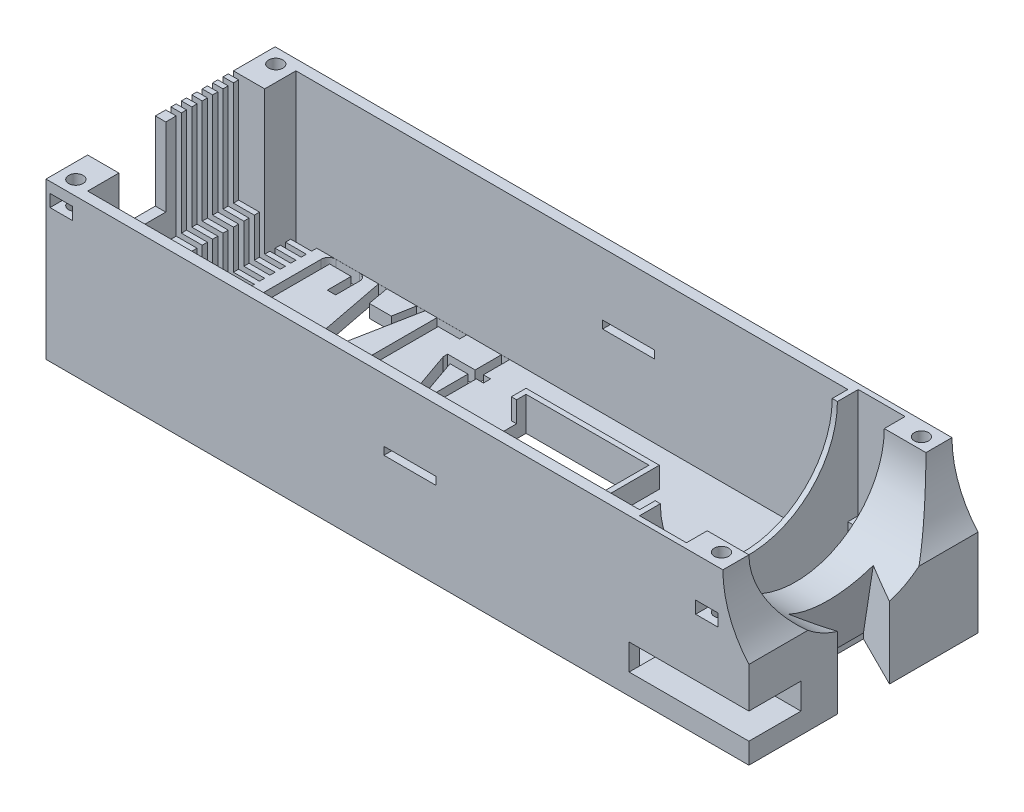
SolidWorks part; units mm, degrees
ref_plane "Front Plane" through (0, 0, 0) normal (0, 0, 1) x (1, 0, 0)
ref_plane "Top Plane" through (0, 0, 0) normal (0, 1, 0) x (1, 0, 0)
ref_plane "Right Plane" through (0, 0, 0) normal (1, 0, 0) x (0, 0, -1)
sketch "Sketch2" plane through (0, 0, 0) normal (0, 1, 0) x (1, 0, 0)
  line L4 (451.485, -2.54) -> (374.015, -2.54)
  line L5 (451.485, -2.54) -> (451.485, 74.93)
  line L6 (451.485, 74.93) -> (374.015, 74.93)
  line L7 (374.015, -2.54) -> (374.015, 74.93)
  line L8 (469.9, -19.685) -> (-50.8, -19.685)
  line L9 (469.9, -19.685) -> (469.9, 92.075)
  line L10 (469.9, 92.075) -> (-50.8, 92.075)
  line L11 (-50.8, -19.685) -> (-50.8, 92.075)
  line L12 (449.58, -0.635) -> (317.5, -0.635)
  line L13 (449.58, -0.635) -> (449.58, 89.789)
  line L14 (449.58, 89.789) -> (317.5, 89.789)
  line L15 (317.5, -0.635) -> (317.5, 89.789)
  line L16 (445.77, 3.175) -> (326.263, 3.175)
  line L17 (445.77, 3.175) -> (445.77, 85.979)
  line L18 (445.77, 85.979) -> (326.263, 85.979)
  line L19 (326.263, 3.175) -> (326.263, 85.979)
  line L20 (326.263, 48.895) -> (313.944, 48.895)
  line L21 (326.263, 48.895) -> (326.263, 77.089)
  line L22 (326.263, 77.089) -> (313.944, 77.089)
  line L23 (313.944, 48.895) -> (313.944, 77.089)
  line L24 (313.944, 68.453) -> (307.34, 68.453)
  line L25 (313.944, 68.453) -> (313.944, 77.089)
  line L26 (313.944, 77.089) -> (307.34, 77.089)
  line L27 (307.34, 68.453) -> (307.34, 77.089)
  line L28 (292.1, 92.075) -> (292.1, -19.685)
  line L33 (292.1, 48.895) -> (266.7, 61.595)
  line L34 (266.7, 61.595) -> (266.7, 10.795)
  line L35 (266.7, 10.795) -> (292.1, 23.495)
  circle A0 centre (412.75, 36.195) radius 20.32
  circle A1 centre (412.75, 36.195) radius 29.21
  dimension "D1" = 40.64
  dimension "D2" = 58.42
  dimension "D3" = 82.804
  dimension "D4" = 90.424
  dimension "D5" = 132.08
  dimension "D6" = 119.507
  dimension "D7" = 3.81
  dimension "D8" = 3.81
  dimension "D9" = 28.194
  dimension "D10" = 8.636
  dimension "D11" = 12.319
  dimension "D12" = 520.7
  dimension "D13" = 33.02
  dimension "D14" = 33.02
  dimension "D15" = 111.76
  dimension "D16" = 77.47
  dimension "D17" = 57.15
  dimension "D18" = 38.735
  dimension "D19" = 77.47
  dimension "D20" = 38.735
  dimension "D21" = 50.8
  dimension "D22" = 8.89
  dimension "D23" = 55.88
  dimension "D24" = 12.7
  dimension "D25" = 25.4
  dimension "D26" = 12.7
  dimension "D27" = 25.4
  dimension "D28" = 177.8
sketch "Sketch3" plane through (0, 0, 0) normal (0, 1, 0) x (1, 0, 0)
  line L1 (-50.8, 92.075) -> (469.9, 92.075)
  line L2 (-50.8, 92.075) -> (-50.8, -19.685)
  line L3 (-50.8, -19.685) -> (469.9, -19.685)
  line L4 (469.9, 92.075) -> (469.9, -19.685)
extrude "Boss-Extrude1" add sketch "Sketch3" along normal blind 73.66
sketch "Sketch4" plane through (0, 0, 19.685) normal (0, 0, 1) x (1, 0, 0)
  line L0 (469.9, 0) -> (254, 0)
  line L1 (-50.8, 0) -> (469.9, 0) construction
  line L2 (469.9, 22.86) -> (330.2, 22.86)
  line L3 (-50.8, 73.66) -> (-50.8, 0) construction
  line L4 (469.9, 73.66) -> (469.9, 0) construction
  line L5 (330.2, 22.86) -> (279.4, 73.66)
  line L7 (469.9, 22.86) -> (469.9, 73.66)
  line L8 (279.4, 73.66) -> (469.9, 73.66)
  circle A0 centre (330.2, 73.66) radius 50.8
  line M3 (469.9, 0) -> (469.9, 73.66)
  line M4 (469.9, 73.66) -> (-50.8, 73.66)
  dimension "D7" = 101.6
  dimension "D1" = 215.9
  dimension "D2" = 139.7
  dimension "D3" = 22.86
  dimension "D4" = 135
  dimension "D5" = 50.8
  dimension "D6" = 330.2
extrude "Cut-Extrude2" cut sketch "Sketch4" against normal blind 156.718 contours A0 L2 M3 M4 | A0 region at (419.355, 46.7249, 19.685)
extrude "Cut-Extrude5" cut sketch "Sketch2" along normal blind 96.52 contours L34 L35 L28 L33 | L10 L28 L8 L9 L24 L27 L26 L22 L15 L14 L13 L6 L5 L4 L7 L12 L20 L23 | L19 L16 L7 L6 L17 L18 | L19 L20 L15 L12 L7 L16 | L27 L24 L23 L26 | L22 L19 L18 L17 L6 L13 L14 L15 | L16 L17 L6 L7 A1 | A0 | A1 A0 | L22 L21 L20 L23 | L12 L15 L14 L13 | L4 L7 L6 L5 region at (345.7575, 0, -0.1165) region at (380.1648, 0, -86.5884) region at (360.119, 0, -50.5692) region at (375.0298, 0, -39.0525) region at (310.642, 0, -72.771) region at (381, 0, 17.5849) region at (277.9889, 0, -36.195) region at (412.75, 0, -36.195) region at (384.3662, 0, -36.195)
sketch "Sketch8" plane through (0, 0, -92.075) normal (0, 0, -1) x (-1, 0, 0)
  line L0 (-266.7, 0) -> (-280.8112, 52.6637)
  line L1 (-280.8112, 52.6637) -> (-120.7737, 52.6637)
  line L3 (-266.7, 0) -> (-106.3833, 0)
  line L4 (-469.9, 0) -> (50.8, 0) construction
  line L5 (-106.3833, 0) -> (-106.3833, 52.6637)
  line L6 (-106.3833, 52.6637) -> (-120.7737, 52.6637)
  point P8 (-135.5488, 59.1548)
  dimension "D1" = 15
extrude "Boss-Extrude2" add sketch "Sketch8" against normal blind 96.52
sketch "Sketch5" plane through (0, 0, 0) normal (1, 0, 0) x (0, 0, -1)
  line L0 (10.795, 73.66) -> (61.595, 73.66) construction
  circle A0 centre (36.195, 73.66) radius 43.18
  dimension "D1" = 86.36
extrude "Cut-Extrude3" cut sketch "Sketch5" along normal blind 304.8 contours A0
sketch "Sketch6" plane through (0, 73.66, 0) normal (0, 1, 0) x (1, 0, 0)
  line L0 (469.9, -19.685) -> (-50.8, -19.685) construction
  line L1 (-45.72, -14.605) -> (233.68, -14.605)
  line L2 (-45.72, -14.605) -> (-45.72, 86.995)
  line L3 (-45.72, 86.995) -> (233.68, 86.995)
  line L4 (233.68, -14.605) -> (233.68, 86.995)
  line L5 (-50.8, -19.685) -> (-50.8, 92.075) construction
  dimension "D1" = 101.6
  dimension "D2" = 5.08
  dimension "D3" = 5.08
  dimension "D4" = 279.4
extrude "Cut-Extrude4" cut sketch "Sketch6" against normal blind 50.8
sketch "Sketch7" plane through (0, 73.66, 0) normal (0, 1, 0) x (1, 0, 0)
  line L0 (245.1614, -13.805) -> (237.4386, -13.805)
  line L1 (231.3, 36.195) -> (251.3, 36.195)
  line L2 (241.3, 36.195) -> (241.3, -13.805)
  line L3 (-45.72, 36.195) -> (169.3056, 36.195)
  line L4 (-45.72, 86.995) -> (-45.72, -14.605) construction
  arc A0 (237.4386, -13.805) -> (231.3, 36.195) centre (438, 36.195) cw
  arc A1 (245.1614, -13.805) -> (251.3, 36.195) centre (44.6, 36.195) ccw
  dimension "D1" = 287.02
revolve "Cut-Revolve1" cut sketch "Sketch7" angle 360 about L3 region at (243.6576, 73.66, 10.203) region at (245.6519, 73.66, -16.5343)
extrude "Boss-Extrude3" add sketch "Sketch2<11>" against normal blind 2.54 contours L35 L34 L33 L28 L10 L11 L8 region at (116.5739, 0, -36.195)
sketch "Sketch2<11>" plane through (0, 0, 0) normal (0, 1, 0) x (1, 0, 0) same geometry as "Sketch2"
sketch "Sketch10" plane through (-50.8, 0, 0) normal (-1, 0, 0) x (0, 0, 1)
  line L0 (-92.075, 73.66) -> (-92.075, -2.54) construction
  line L1 (-84.455, -15.24) -> (-86.995, -15.24)
  line L2 (-84.455, -15.24) -> (-84.455, 86.36)
  line L3 (-84.455, 86.36) -> (-86.995, 86.36)
  line L4 (-86.995, -15.24) -> (-86.995, 86.36)
  line L5 (-79.375, -15.24) -> (-81.915, -15.24)
  line L6 (-79.375, -15.24) -> (-79.375, 86.36)
  line L7 (-79.375, 86.36) -> (-81.915, 86.36)
  line L8 (-81.915, -15.24) -> (-81.915, 86.36)
  line L9 (-74.295, -15.24) -> (-76.835, -15.24)
  line L10 (-74.295, -15.24) -> (-74.295, 86.36)
  line L11 (-74.295, 86.36) -> (-76.835, 86.36)
  line L12 (-76.835, -15.24) -> (-76.835, 86.36)
  line L13 (-69.215, -15.24) -> (-71.755, -15.24)
  line L14 (-69.215, -15.24) -> (-69.215, 86.36)
  line L15 (-69.215, 86.36) -> (-71.755, 86.36)
  line L16 (-71.755, -15.24) -> (-71.755, 86.36)
  line L17 (-64.135, -15.24) -> (-66.675, -15.24)
  line L18 (-64.135, -15.24) -> (-64.135, 86.36)
  line L19 (-64.135, 86.36) -> (-66.675, 86.36)
  line L20 (-66.675, -15.24) -> (-66.675, 86.36)
  line L21 (-59.055, -15.24) -> (-61.595, -15.24)
  line L22 (-59.055, -15.24) -> (-59.055, 86.36)
  line L23 (-59.055, 86.36) -> (-61.595, 86.36)
  line L24 (-61.595, -15.24) -> (-61.595, 86.36)
  line L25 (-53.975, -15.24) -> (-56.515, -15.24)
  line L26 (-53.975, -15.24) -> (-53.975, 86.36)
  line L27 (-53.975, 86.36) -> (-56.515, 86.36)
  line L28 (-56.515, -15.24) -> (-56.515, 86.36)
  line L29 (-48.895, -15.24) -> (-51.435, -15.24)
  line L30 (-48.895, -15.24) -> (-48.895, 86.36)
  line L31 (-48.895, 86.36) -> (-51.435, 86.36)
  line L32 (-51.435, -15.24) -> (-51.435, 86.36)
  line L33 (-43.815, -15.24) -> (-46.355, -15.24)
  line L34 (-43.815, -15.24) -> (-43.815, 86.36)
  line L35 (-43.815, 86.36) -> (-46.355, 86.36)
  line L36 (-46.355, -15.24) -> (-46.355, 86.36)
  line L37 (-38.735, -15.24) -> (-41.275, -15.24)
  line L38 (-38.735, -15.24) -> (-38.735, 86.36)
  line L39 (-38.735, 86.36) -> (-41.275, 86.36)
  line L40 (-41.275, -15.24) -> (-41.275, 86.36)
  line L41 (-92.075, 73.66) -> (19.685, 73.66) construction
  line L42 (-86.995, 86.36) -> (-38.735, 86.36)
  line L43 (-86.995, 86.36) -> (-86.995, 83.82)
  line L44 (-86.995, 83.82) -> (-38.735, 83.82)
  line L45 (-38.735, 86.36) -> (-38.735, 83.82)
  line L51 (11.7349, 35.56) -> (-33.655, 35.56)
  line L52 (11.7349, 35.56) -> (11.7349, 73.66)
  line L53 (11.7349, 73.66) -> (-33.655, 73.66)
  line L54 (-33.655, 35.56) -> (-33.655, 73.66)
  dimension "D1" = 2.54
  dimension "D2" = 5.08
  dimension "D3" = 10
  dimension "D4" = 101.6
  dimension "D5" = 2.54
  dimension "D6" = 12.7
  dimension "D7" = 5.08
  dimension "D8" = 38.1
extrude "Cut-Extrude6" cut sketch "Sketch10" against normal blind 25.4 contours L38 L37 L40 L39 | L36 L35 L34 L33 | L32 L31 L30 L29 | L28 L27 L26 L25 | L24 L23 L22 L21 | L20 L19 L18 L17 | L16 L15 L14 L13 | L3 L2 L1 L4 | L6 L7 L8 L5 | L10 L11 L12 L9 | L52 L51 L54 L53
sketch "Sketch11" plane through (0, -2.54, 0) normal (0, -1, 0) x (1, 0, 0)
  text T0 "CAL4" font "Agency FB" height 48.26
extrude "Cut-Extrude7" cut sketch "Sketch11" against normal blind 50.8
sketch "Sketch13" plane through (0, 73.66, 0) normal (0, 1, 0) x (1, 0, 0)
  line L1 (-50.8, -19.685) -> (-35.56, -19.685)
  line L2 (-50.8, -19.685) -> (-50.8, 0.635)
  line L3 (-50.8, 0.635) -> (-35.56, 0.635)
  line L4 (-35.56, -19.685) -> (-35.56, 0.635)
  line L7 (-50.8, 92.075) -> (-35.56, 92.075)
  line L9 (-50.8, 92.075) -> (-50.8, 71.755)
  line L10 (-50.8, 71.755) -> (-35.56, 71.755)
  line L11 (-35.56, 92.075) -> (-35.56, 71.755)
  dimension "D1" = 15.24
  dimension "D2" = 20.32
  dimension "D3" = 15.24
  dimension "D4" = 20.32
extrude "Boss-Extrude4" add sketch "Sketch13" against normal up to surface (76.2 mm away) up to face at (14.8534, -2.54, -73.8982)
sketch "Sketch14" plane through (0, 0, 19.685) normal (0, 0, 1) x (1, 0, 0)
  line L0 (-50.8, 73.66) -> (279.4, 73.66) construction
  line L1 (-37.846, 62.58) -> (-48.846, 62.58)
  line L2 (-37.846, 62.58) -> (-37.846, 68.58)
  line L3 (-37.846, 68.58) -> (-48.846, 68.58)
  line L4 (-48.846, 62.58) -> (-48.846, 68.58)
  line L5 (-50.8, 73.66) -> (-50.8, -2.54) construction
  line L7 (277.114, 48.26) -> (266.114, 48.26)
  line L8 (277.114, 48.26) -> (277.114, 54.26)
  line L9 (277.114, 54.26) -> (266.114, 54.26)
  line L10 (266.114, 48.26) -> (266.114, 54.26)
  point P12 (-43.346, 68.58)
  point P13 (271.614, 54.26)
  dimension "D1" = 5.08
  dimension "D2" = 11
  dimension "D3" = 6
  dimension "D4" = 12.954
  dimension "D5" = 11
  dimension "D6" = 314.96
  dimension "D7" = 25.4
  dimension "D8" = 6
extrude "Cut-Extrude8" cut sketch "Sketch14" against normal blind 14
sketch "Sketch15" plane through (0, 48.26, 0) normal (0, 1, 0) x (1, 0, 0)
  line L0 (277.114, -19.685) -> (266.114, -19.685)
  line L2 (271.614, -18.9239) -> (277.114, -15.7484)
  line L3 (277.114, -15.7484) -> (277.114, -9.3976)
  line L4 (277.114, -9.3976) -> (271.614, -6.2221)
  line L5 (271.614, -6.2221) -> (266.114, -9.3976)
  line L6 (266.114, -9.3976) -> (266.114, -15.7484)
  line L7 (266.114, -15.7484) -> (271.614, -18.9239)
  line L8 (271.614, -12.573) -> (-43.346, -12.573)
  line L9 (-50.8, -19.685) -> (-50.8, 38.735) construction
  line L10 (298.0072, 36.195) -> (204.1834, 36.195)
  line L11 (271.614, 84.963) -> (-43.346, 84.963)
  line L12 (266.114, 88.1384) -> (271.614, 91.3139)
  line L13 (266.114, 81.7876) -> (266.114, 88.1384)
  line L14 (271.614, 78.6121) -> (266.114, 81.7876)
  line L15 (277.114, 81.7876) -> (271.614, 78.6121)
  line L16 (277.114, 88.1384) -> (277.114, 81.7876)
  line L17 (271.614, 91.3139) -> (277.114, 88.1384)
  line L18 (277.114, 92.075) -> (266.114, 92.075)
  line L19 (292.1, -19.685) -> (-50.8, -19.685) construction
  line L20 (279.4, 92.075) -> (-50.8, 92.075) construction
  circle A0 centre (271.614, -12.573) radius 5.5 construction
  circle A1 centre (271.614, -12.573) radius 3.5
  circle A2 centre (-43.346, -12.573) radius 3.5
  circle A3 centre (271.614, 84.963) radius 5.5 construction
  circle A4 centre (-43.346, 84.963) radius 3.5
  circle A5 centre (271.614, 84.963) radius 3.5
  ellipse E0 centre (286.4371, 36.195) end of major axis (286.4371, -6.985) minor radius 11.57 (276.2708, 56.8096) -> (276.2708, 15.5804) ccw construction
  dimension "D3" = 7
  dimension "D5" = 7
  dimension "D1" = 11
  dimension "D2" = 7.112
  dimension "D4" = 7.454
  dimension "D6" = 314.96
  dimension "D7" = 7.112
  dimension "D8" = 7.112
extrude "Cut-Extrude9" cut sketch "Sketch15" along normal blind 406.4 and the other way blind 5.08 contours A2 | A4 | A5 | A1
extrude "Cut-Extrude10" cut sketch "Sketch14<2>" along normal blind 14 from surface starting at face at (151.7862, 36.2278, -92.075)
sketch "Sketch14<2>" plane through (0, 0, 19.685) normal (0, 0, 1) x (1, 0, 0) same geometry as "Sketch14"
sketch "Sketch18" plane through (0, 22.86, 0) normal (0, 1, 0) x (1, 0, 0)
  line L1 (-35.56, 86.995) -> (233.68, 86.995)
  line L2 (-35.56, 86.995) -> (-35.56, -14.605)
  line L3 (-35.56, -14.605) -> (233.68, -14.605)
  line L4 (233.68, 86.995) -> (233.68, -14.605)
extrude "Cut-Extrude12" cut sketch "Sketch18" against normal blind 19.05
sketch "Sketch19" plane through (0, 3.81, 0) normal (0, 1, 0) x (1, 0, 0)
  line L0 (9.6709, 73.6836) -> (23.9266, 73.6836)
  line L1 (23.9266, 73.6836) -> (16.7987, 40.2137)
  line L2 (16.7987, 40.2137) -> (9.6709, 73.6836)
extrude "Cut-Extrude13" cut sketch "Sketch19" against normal blind 20.32
sketch "Sketch20" plane through (0, -2.54, 0) normal (0, -1, 0) x (1, 0, 0)
  line L0 (233.68, 6.985) -> (233.68, -79.375) construction
  line L1 (97.536, -6.223) -> (157.48, -6.223)
  line L2 (97.536, -6.223) -> (97.536, -66.167)
  line L3 (97.536, -66.167) -> (157.48, -66.167)
  line L4 (157.48, -6.223) -> (157.48, -66.167)
  line L6 (292.1, 19.685) -> (-50.8, 19.685) construction
  point P6 (97.536, -36.195)
  dimension "D1" = 59.944
  dimension "D2" = 59.944
  dimension "D3" = 76.2
  dimension "D4" = 55.88
extrude "Cut-Extrude14" cut sketch "Sketch20" against normal blind 73 contours L3 L4 L1 L2
sketch "Sketch21" plane through (0, 3.81, 0) normal (0, 1, 0) x (1, 0, 0)
  line L0 (157.48, 6.223) -> (97.536, 6.223) construction
  line L1 (157.48, 66.167) -> (157.48, 6.223) construction
  line L2 (97.536, 66.167) -> (97.536, 6.223) construction
  line L3 (157.48, 66.167) -> (97.536, 66.167) construction
  line L4 (157.48, 6.223) -> (97.536, 6.223)
  line L5 (157.48, 66.167) -> (157.48, 6.223)
  line L6 (97.536, 66.167) -> (97.536, 6.223)
  line L7 (157.48, 66.167) -> (97.536, 66.167)
  line L8 (160.02, 3.683) -> (94.996, 3.683)
  line L9 (94.996, 68.707) -> (94.996, 3.683)
  line L10 (160.02, 68.707) -> (94.996, 68.707)
  line L11 (160.02, 68.707) -> (160.02, 3.683)
  dimension "D1" = 2.54
extrude "Boss-Extrude5" add sketch "Sketch21" along normal blind 10.16
sketch "Sketch22" plane through (0, 13.97, 0) normal (0, 1, 0) x (1, 0, 0)
  line L0 (97.536, 66.167) -> (97.536, 6.223) construction
  line L1 (107.974, 10.841) -> (87.098, 10.841)
  line L2 (107.974, 10.841) -> (107.974, 61.549)
  line L3 (107.974, 61.549) -> (87.098, 61.549)
  line L4 (87.098, 10.841) -> (87.098, 61.549)
  line L5 (107.974, 10.841) -> (87.098, 61.549) construction
  line L6 (107.974, 61.549) -> (87.098, 10.841) construction
  point P0 (97.536, 36.195)
extrude "Cut-Extrude15" cut sketch "Sketch22" against normal blind 10.16
sketch "Sketch23" plane through (0, 0, 19.685) normal (0, 0, 1) x (1, 0, 0)
  line L0 (292.1, -2.54) -> (-50.8, -2.54) construction
  line L1 (139.446, 39.37) -> (114.046, 39.37)
  line L2 (139.446, 39.37) -> (139.446, 43.18)
  line L3 (139.446, 43.18) -> (114.046, 43.18)
  line L4 (114.046, 39.37) -> (114.046, 43.18)
  line L5 (97.536, 13.97) -> (97.536, -2.54) construction
  dimension "D1" = 3.81
  dimension "D2" = 25.4
  dimension "D3" = 41.91
  dimension "D4" = 16.51
extrude "Cut-Extrude16" cut sketch "Sketch23" against normal blind 187.96
sketch "Sketch24" plane through (292.1, 0, 0) normal (1, 0, 0) x (0, 0, -1)
  line L1 (5.715, 7.62) -> (-29.8645, 7.62)
  line L2 (-29.8645, 7.62) -> (-29.8645, 20.32)
  line L3 (-29.8645, 20.32) -> (5.715, 20.32)
  line L10 (5.715, 7.62) -> (5.715, 20.32)
  line L11 (-19.685, 40.059) -> (-19.685, -2.54) construction
  line L13 (23.495, -2.54) -> (-19.685, -2.54) construction
  dimension "D1" = 25.4
  dimension "D2" = 22.86
  dimension "D3" = 12.7
extrude "Cut-Extrude17" cut sketch "Sketch24" against normal up to surface (58.42 mm away) up to face at (233.68, 43.18, -36.195)
sketch "Sketch25" plane through (0, 73.66, 0) normal (0, 1, 0) x (1, 0, 0)
  line L0 (-50.8, -19.685) -> (279.4, -19.685) construction
  line L1 (259.08, -17.145) -> (236.22, -17.145)
  line L2 (259.08, -17.145) -> (259.08, 89.535)
  line L3 (259.08, 89.535) -> (236.22, 89.535)
  line L4 (236.22, -17.145) -> (236.22, 89.535)
  line L5 (279.4, 92.075) -> (-50.8, 92.075) construction
  line L6 (233.68, -14.605) -> (233.68, 86.995) construction
  dimension "D1" = 2.54
  dimension "D2" = 2.54
  dimension "D3" = 2.54
  dimension "D4" = 22.86
extrude "Cut-Extrude18" cut sketch "Sketch25" against normal blind 53.34 contours L1 L4 L3 L2
sketch "Sketch26" plane through (0, 20.32, 0) normal (0, 1, 0) x (1, 0, 0)
  line L0 (259.08, 5.715) -> (259.08, 89.535) construction
  line L1 (259.08, 48.895) -> (236.22, 48.895)
  line L2 (259.08, 48.895) -> (259.08, 23.495)
  line L3 (259.08, 23.495) -> (236.22, 23.495)
  line L4 (236.22, 48.895) -> (236.22, 23.495)
  line L5 (259.08, 48.895) -> (236.22, 23.495) construction
  line L6 (259.08, 23.495) -> (236.22, 48.895) construction
  point P0 (247.65, 36.195)
  dimension "D1" = 11.43
  dimension "D2" = 22.86
  dimension "D3" = 25.4
extrude "Cut-Extrude19" cut sketch "Sketch26" against normal blind 52.54
sketch "Sketch27" plane through (0, 20.32, 0) normal (0, 1, 0) x (1, 0, 0)
  line L0 (259.08, 48.895) -> (259.08, 89.535) construction
  line L1 (259.08, 84.455) -> (236.22, 84.455)
  line L2 (259.08, 84.455) -> (259.08, 10.795)
  line L3 (259.08, 10.795) -> (236.22, 10.795)
  line L4 (236.22, 84.455) -> (236.22, 10.795)
  line L5 (236.22, 5.715) -> (236.22, 23.495) construction
  line L6 (259.08, 89.535) -> (236.22, 89.535) construction
  line L7 (236.22, 5.715) -> (259.08, 5.715) construction
  dimension "D1" = 5.08
  dimension "D2" = 5.08
extrude "Cut-Extrude20" cut sketch "Sketch27" against normal blind 15.24
